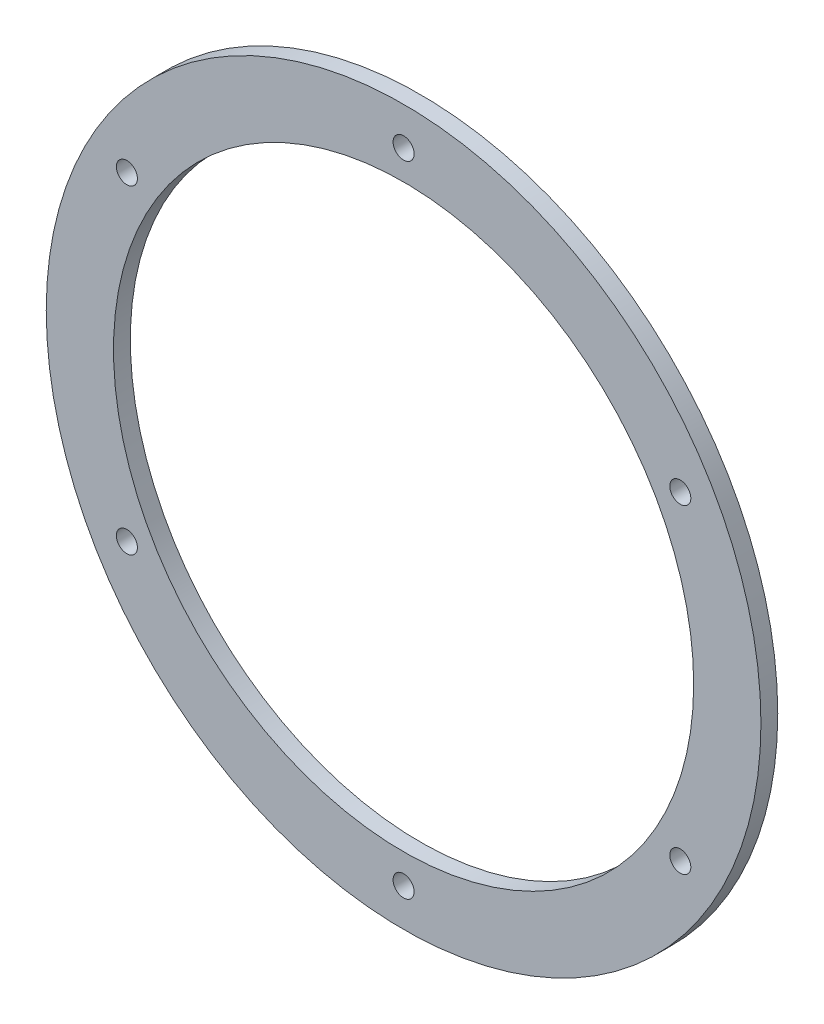
SolidWorks part; units mm, degrees
ref_plane "Front" through (0, 0, 0) normal (0, 0, 1) x (1, 0, 0)
ref_plane "Top" through (0, 0, 0) normal (0, 1, 0) x (1, 0, 0)
ref_plane "Right" through (0, 0, 0) normal (1, 0, 0) x (0, 0, -1)
sketch "Эскиз1" plane through (0, 0, 0) normal (0, 0, 1) x (1, 0, 0)
  circle A0 centre (0, 0) radius 42.5
  circle A1 centre (0, 0) radius 34.5
  dimension "D1" = 85
  dimension "D2" = 69
extrude "Уплотнительное кольцо" add sketch "Эскиз1" along normal blind 2
sketch "Эскиз3" plane through (0, 0, 2) normal (0, 0, 1) x (1, 0, 0)
  circle A2 centre (0, 38) radius 1.25
  dimension "D1" = 2.5
  dimension "D2" = 38
extrude "Под шуруп" cut sketch "Эскиз3" against normal through all
pattern_circular "Под шурупы по окружности" count 6 over 360 about axis through (0, 0, 2) along (0, 0, -1) of "Под шуруп"
